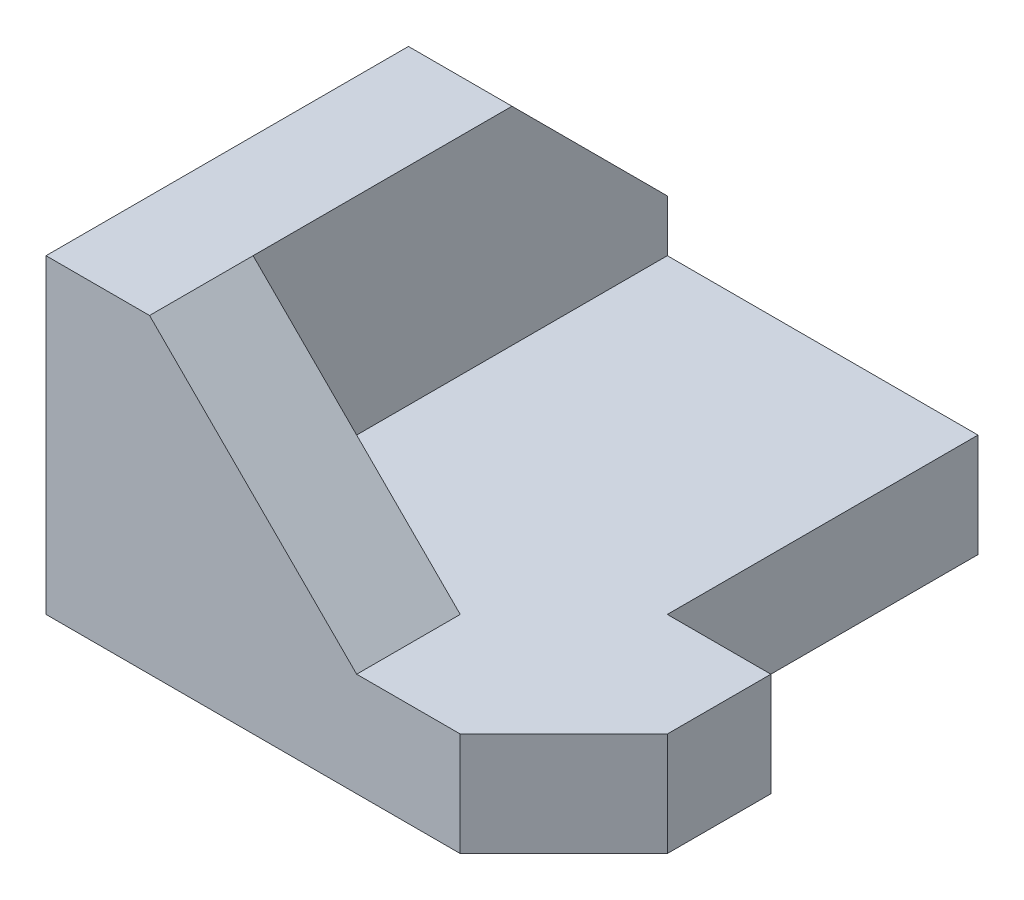
SolidWorks part; units mm, degrees
ref_plane "Front Plane" through (0, 0, 0) normal (0, 0, 1) x (1, 0, 0)
ref_plane "Top Plane" through (0, 0, 0) normal (0, 1, 0) x (1, 0, 0)
ref_plane "Right Plane" through (0, 0, 0) normal (1, 0, 0) x (0, 0, -1)
sketch "Sketch1" plane through (0, 0, 0) normal (0, 1, 0) x (1, 0, 0)
  line L0 (0, 0) -> (0, 50)
  line L1 (0, 50) -> (40, 50)
  line L2 (40, 50) -> (40, 20)
  line L3 (40, 20) -> (50, 20)
  line L4 (50, 20) -> (50, 0)
  line L5 (50, 0) -> (0, 0)
  line L6 (10, 50) -> (10, 0)
  dimension "D1" = 50
  dimension "D2" = 40
  dimension "D3" = 30
  dimension "D4" = 10
  dimension "D5" = 10
extrude "Boss-Extrude1" add sketch "Sketch1" along normal blind 30 contours L6 L1 L0 L5 region at (5, 0, -25)
extrude "Boss-Extrude2" add sketch "Sketch1<3>" along normal blind 10 contours L1 L6 L5 L4 L3 L2 region at (27.3529, 0, -23.2353)
sketch "Sketch1<3>" plane through (0, 0, 0) normal (0, 1, 0) x (1, 0, 0) same geometry as "Sketch1"
chamfer "Chamfer1" distance 10 angle 45 1 edges at (50, 5, 0)
chamfer "Chamfer2" distance 15 angle 45 1 edges at (5, 30, -50)
sketch "Sketch2" plane through (0, 0, 0) normal (0, 0, 1) x (1, 0, 0)
  line L0 (10, 10) -> (30, 10)
  line L1 (40, 10) -> (10, 10) construction
  line L2 (30, 10) -> (10, 30)
  line L3 (10, 30) -> (10, 10)
  dimension "D1" = 20
extrude "Boss-Extrude3" add sketch "Sketch2" against normal blind 10
